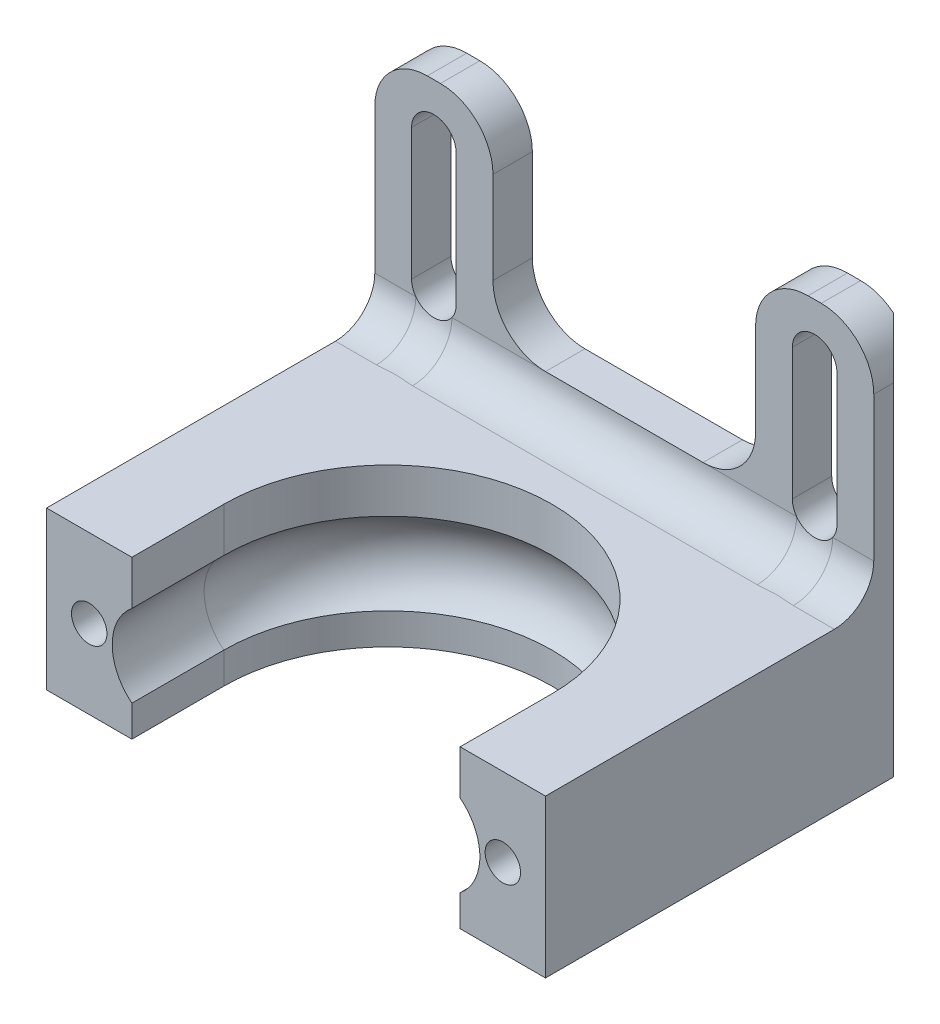
SolidWorks part; units mm, degrees
ref_plane "Front" through (0, 0, 0) normal (0, 0, 1) x (1, 0, 0)
ref_plane "Top" through (0, 0, 0) normal (0, 1, 0) x (1, 0, 0)
ref_plane "Right" through (0, 0, 0) normal (1, 0, 0) x (0, 0, -1)
sketch "Эскиз1" plane through (0, 0, 0) normal (0, 0, 1) x (1, 0, 0)
  line L0 (-19, -39) -> (-19, -13)
  line L1 (-15, -9) -> (-14, -9)
  line L2 (-10, -13) -> (-10, -20)
  line L3 (-6, -24) -> (6, -24)
  line L4 (10, -20) -> (10, -13)
  line L5 (14, -9) -> (15, -9)
  line L6 (19, -13) -> (19, -39)
  line L7 (19, -39) -> (-19, -39)
  line L8 (0, -46) -> (0, -4.5059) construction
  line L10 (-14.5, -13) -> (-14.5, -23) construction
  line L11 (-12.8, -13) -> (-12.8, -23)
  line L12 (-16.2, -13) -> (-16.2, -23)
  line L13 (14.5, -13) -> (14.5, -23) construction
  line L14 (12.8, -13) -> (12.8, -23)
  line L15 (16.2, -13) -> (16.2, -23)
  line L16 (-10, -13) -> (-19, -13) construction
  arc A0 (-12.8, -13) -> (-16.2, -13) centre (-14.5, -13) ccw
  arc A1 (-16.2, -23) -> (-12.8, -23) centre (-14.5, -23) ccw
  arc A2 (6, -24) -> (10, -20) centre (6, -20) ccw
  arc A3 (-10, -20) -> (-6, -24) centre (-6, -20) ccw
  arc A4 (15, -9) -> (19, -13) centre (15, -13) cw
  arc A5 (10, -13) -> (14, -9) centre (14, -13) cw
  arc A6 (-19, -13) -> (-15, -9) centre (-15, -13) cw
  arc A7 (-10, -13) -> (-14, -9) centre (-14, -13) ccw
  arc A8 (12.8, -13) -> (16.2, -13) centre (14.5, -13) cw
  arc A9 (16.2, -23) -> (12.8, -23) centre (14.5, -23) cw
  point P13 (-14.5, -18)
  point P35 (14.5, -18)
  dimension "D7" = 1.7
  dimension "D9" = 4
  dimension "D1" = 38
  dimension "D2" = 30
  dimension "D5" = 10
  dimension "D10" = 15
extrude "Бобышка-Вытянуть1" add sketch "Эскиз1" along normal blind 3
sketch "Эскиз2" plane through (0, -39, 0) normal (0, -1, 0) x (1, 0, 0)
  line L0 (-19, 3) -> (-19, 28)
  line L1 (-19, 28) -> (-12.5, 28)
  line L2 (-12.5, 28) -> (-12.5, 21)
  line L3 (-19, 3) -> (19, 3)
  line L4 (12.5, 21) -> (12.5, 28)
  line L5 (12.5, 28) -> (19, 28)
  line L6 (19, 28) -> (19, 3)
  line L10 (-19, 0) -> (19, 0)
  line L11 (19, 0) -> (19, 3)
  line L12 (19, 3) -> (-19, 3)
  line L13 (-19, 3) -> (-19, 0)
  line L14 (-19, 0) -> (19, 0)
  line L15 (19, 0) -> (19, 3)
  line L17 (-19, 3) -> (-19, 0)
  arc A0 (-12.5, 21) -> (12.5, 21) centre (0, 21) ccw
  line M14 (19, 3) -> (-19, 3)
  dimension "D1" = 25
  dimension "D2" = 25
  dimension "D3" = 0
extrude "Бобышка-Вытянуть2" add sketch "Эскиз2" against normal blind 12 from offset 0 contours A0 L2 L1 L0 L6 L5 L4 M14 region at (-18.5451, -39, 15.5)
ref_plane "Плоскость1" through (0, 0, 21) normal (0, 0, 1) x (1, 0, 0)
sketch "Эскиз3" plane through (0, 0, 21) normal (0, 0, 1) x (1, 0, 0)
  line L0 (0, -39) -> (0, -15.0423) construction
  line L1 (-12.5, -39) -> (12.5, -39) construction
  line L2 (-10, -33.5) -> (10, -33.5)
  circle A0 centre (-10, -33.5) radius 4
  circle A1 centre (10, -33.5) radius 4
  point P7 (-10.9786, -33.5)
  point P9 (0, -33.5)
  dimension "D1" = 8
  dimension "D2" = 20
revolve "Вырез-Повернуть1" cut sketch "Эскиз3" angle 360 about L0 region at (-13.8869, -33.5, 21)
extrude "Вырез-Вытянуть1" cut sketch "Эскиз3<8>" along normal blind 10 contours A1 | A0 region at (10, -29.6131, 21)
sketch "Эскиз3<8>" plane through (0, 0, 21) normal (0, 0, 1) x (1, 0, 0) same geometry as "Эскиз3"
sketch "Эскиз4" plane through (0, 0, 28) normal (0, 0, 1) x (1, 0, 0)
  line L0 (19, -27) -> (12.5, -39) construction
  line L1 (-12.5, -39) -> (-19, -27) construction
  line L2 (-19, -39) -> (-12.5, -39) construction
  circle A0 centre (15.75, -33) radius 1.35
  circle A1 centre (-15.75, -33) radius 1.35
  point P13 (-12.5, -39)
  point P15 (19, -27)
extrude "Вырез-Вытянуть2" cut sketch "Эскиз4" against normal blind 10
fillet "Скругление1" radius 3 1 edges at (0, -27, 3)
chamfer "Фаска1" distance 1.5 angle 45 2 edges at (19, -26, 0) (-19, -26, 0) tangent propagation no
